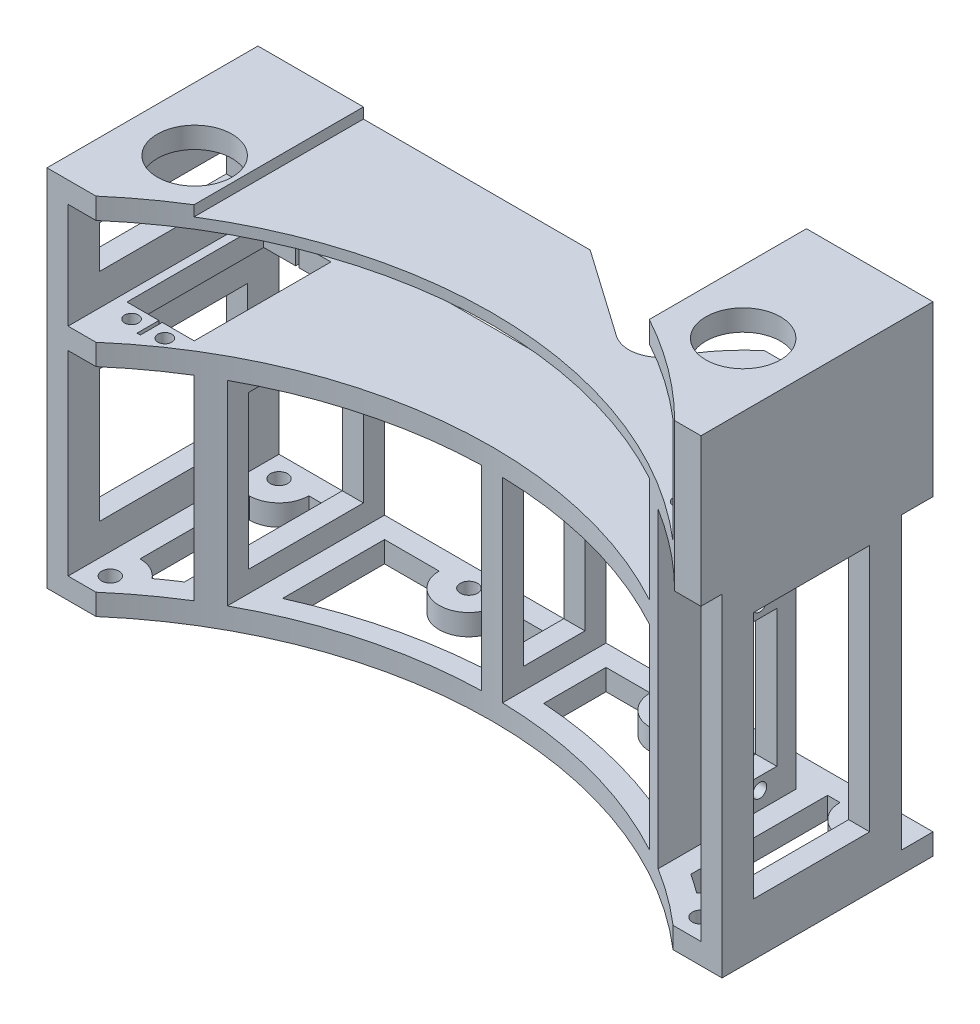
SolidWorks part; units mm, degrees
ref_plane "Front Plane" through (0, 0, 0) normal (0, 0, 1) x (1, 0, 0)
ref_plane "Top Plane" through (0, 0, 0) normal (0, 1, 0) x (1, 0, 0)
ref_plane "Right Plane" through (0, 0, 0) normal (1, 0, 0) x (0, 0, -1)
sketch "Sketch1" plane through (0, 0, 0) normal (0, 0, 1) x (1, 0, 0)
  line L0 (-101.6, 106.425) -> (101.6, 106.425)
  line L1 (-101.6, 0) -> (101.6, 0)
  line L2 (-101.6, 0) -> (-101.6, 106.425)
  line L4 (101.6, 0) -> (101.6, 106.425)
  point P5 (0, 0)
  dimension "D1" = 203.2
  dimension "D2" = 106.425
extrude "Boss-Extrude1" add sketch "Sketch1" along normal mid plane 63.5 contours L1 L4 L0 L2 | L0 region at (0, 53.2125, 0)
sketch "Sketch4" plane through (0, 0, -31.75) normal (0, 0, -1) x (-1, 0, 0)
  line L0 (-101.6, 0) -> (-101.6, 106.425) construction
  line L1 (101.6, 0) -> (101.6, 106.425) construction
  line L2 (-95.25, 103.25) -> (95.25, 103.25)
  line L3 (-95.25, 103.25) -> (-95.25, 71.5)
  line L4 (-95.25, 71.5) -> (95.25, 71.5)
  line L5 (95.25, 103.25) -> (95.25, 71.5)
  line L11 (-95.25, 65.15) -> (95.25, 65.15)
  line L12 (-95.25, 65.15) -> (-95.25, 6.35)
  line L13 (-95.25, 6.35) -> (95.25, 6.35)
  line L14 (95.25, 65.15) -> (95.25, 6.35)
  line L15 (101.6, 0) -> (-101.6, 0) construction
  dimension "D4" = 6.35
  dimension "D1" = 6.35
  dimension "D2" = 71.5
  dimension "D3" = 6.35
  dimension "D5" = 6.35
  dimension "D6" = 31.75
extrude "Cut-Extrude2" cut sketch "Sketch4" against normal through all
sketch "Sketch8" plane through (0, 0, 0) normal (0, 0, 1) x (1, 0, 0)
  line L0 (-95.25, 65.15) -> (95.25, 65.15) construction
  line L1 (-69.85, 65.15) -> (-63.5, 65.15)
  line L2 (-69.85, 65.15) -> (-69.85, 6.35)
  line L3 (-69.85, 6.35) -> (-63.5, 6.35)
  line L4 (-63.5, 65.15) -> (-63.5, 6.35)
  line L5 (95.25, 6.35) -> (-95.25, 6.35) construction
  line L6 (-95.25, 103.25) -> (95.25, 103.25) construction
  line L7 (63.5, 103.25) -> (69.85, 103.25)
  line L8 (63.5, 103.25) -> (63.5, 6.35)
  line L9 (63.5, 6.35) -> (69.85, 6.35)
  line L10 (69.85, 103.25) -> (69.85, 6.35)
  line L11 (95.25, 65.15) -> (95.25, 6.35) construction
  line L12 (-95.25, 6.35) -> (-95.25, 65.15) construction
  line L13 (-101.6, 0) -> (101.6, 0) construction
  line L14 (-3.175, 65.15) -> (3.175, 65.15)
  line L15 (-3.175, 65.15) -> (-3.175, 6.35)
  line L16 (-3.175, 6.35) -> (3.175, 6.35)
  line L17 (3.175, 65.15) -> (3.175, 6.35)
  point P24 (0, 0)
  point P25 (0, 6.35)
  dimension "D1" = 6.35
  dimension "D2" = 6.35
  dimension "D3" = 25.4
  dimension "D4" = 25.4
  dimension "D5" = 6.35
extrude "Boss-Extrude2" add sketch "Sketch8" along normal up to surface (31.75 mm away) from surface up to face at (0, 87.375, 31.75) starting at face at (0, 87.375, -31.75)
sketch "Sketch15" plane through (0, 103.25, 0) normal (0, -1, 0) x (1, 0, 0)
  line L4 (69.85, 31.75) -> (69.85, -31.75)
  line L5 (69.85, -31.75) -> (95.25, -31.75)
  line L6 (95.25, -31.75) -> (95.25, 31.75)
  line L7 (95.25, 31.75) -> (69.85, 31.75)
  line L8 (69.85, 31.75) -> (69.85, -31.75)
  line L9 (69.85, -31.75) -> (95.25, -31.75)
  line L10 (95.25, -31.75) -> (95.25, 31.75)
  line L11 (95.25, 31.75) -> (69.85, 31.75)
  dimension "D1" = 0
extrude "Boss-Extrude4" add sketch "Sketch15" along normal blind 3.175
sketch "Sketch2" plane through (0, 71.5, 0) normal (0, 1, 0) x (1, 0, 0)
  line L0 (-92.677, 24.55) -> (-72.423, -16.604) construction
  line L29 (-92.677, 24.55) -> (-83.05, 24.55)
  line L30 (-92.677, 24.55) -> (-92.677, -16.604)
  line L31 (-92.677, -16.604) -> (-83.05, -16.604)
  line L34 (-72.423, 24.55) -> (-72.423, -16.604)
  line L58 (69.85, 31.75) -> (69.85, -31.75)
  line L59 (69.85, -31.75) -> (95.25, -31.75)
  line L60 (95.25, -31.75) -> (95.25, 31.75)
  line L61 (95.25, 31.75) -> (69.85, 31.75)
  line L62 (69.85, 31.75) -> (69.85, -31.75)
  line L63 (69.85, -31.75) -> (95.25, -31.75)
  line L64 (95.25, -31.75) -> (95.25, 31.75)
  line L65 (95.25, 31.75) -> (69.85, 31.75)
  line L78 (-72.423, 24.55) -> (-92.677, -16.604) construction
  line L79 (-87.55, 28.273) -> (-77.55, -20.327) construction
  line L80 (-87.55, -20.327) -> (-77.55, 28.273) construction
  line L81 (-82.05, -16.604) -> (-72.423, -16.604)
  line L82 (-82.05, -16.604) -> (-82.05, -23.208)
  line L83 (-82.05, -23.208) -> (-83.05, -23.208)
  line L84 (-83.05, -16.604) -> (-83.05, -23.208)
  line L85 (-82.55, 3.973) -> (-13.3966, 3.973) construction
  line L86 (-82.05, 31.154) -> (-83.05, 31.154)
  line L87 (-82.05, 24.55) -> (-82.05, 31.154)
  line L88 (-83.05, 24.55) -> (-83.05, 31.154)
  line L89 (-82.05, 24.55) -> (-72.423, 24.55)
  line L90 (-101.6, -31.75) -> (101.6, -31.75) construction
  line L91 (-101.6, -31.75) -> (-101.6, 31.75) construction
  circle A12 centre (-87.55, -20.327) radius 2.1
  circle A13 centre (-77.55, -20.327) radius 2.1
  circle A14 centre (-87.55, 28.273) radius 2.1
  circle A15 centre (-77.55, 28.273) radius 2.1
  point P8 (-82.55, -23.208)
  point P17 (-82.55, 3.973)
  point P18 (-82.55, 3.973)
  point P27 (-82.55, -6.35)
  dimension "D3" = 48.6
  dimension "D4" = 4.2
  dimension "D2" = 10
  dimension "D5" = 41.154
  dimension "D6" = 20.254
  dimension "D7" = 1
  dimension "D8" = 6.604
  dimension "D9" = 30.9
  dimension "D10" = 25.4
  dimension "D11" = 0
  dimension "D12" = 19.05
extrude "Cut-Extrude3" cut sketch "Sketch2" against normal up to next
sketch "Sketch9" plane through (0, 106.425, 0) normal (0, 1, 0) x (1, 0, 0)
  line L0 (72.423, 24.55) -> (92.677, -16.604) construction
  line L1 (72.423, 24.55) -> (82.05, 24.55)
  line L2 (72.423, 24.55) -> (72.423, -16.604)
  line L3 (72.423, -16.604) -> (82.05, -16.604)
  line L4 (92.677, 24.55) -> (92.677, -16.604)
  line L5 (92.677, 24.55) -> (72.423, -16.604) construction
  line L6 (77.55, 28.273) -> (87.55, -20.327) construction
  line L7 (77.55, -20.327) -> (87.55, 28.273) construction
  line L8 (83.05, -16.604) -> (92.677, -16.604)
  line L9 (83.05, -16.604) -> (83.05, -23.208)
  line L10 (83.05, -23.208) -> (82.05, -23.208)
  line L11 (82.05, -16.604) -> (82.05, -23.208)
  line L12 (82.55, 3.973) -> (164.4034, 3.973) construction
  line L13 (83.05, 31.154) -> (82.05, 31.154)
  line L14 (83.05, 24.55) -> (83.05, 31.154)
  line L15 (82.05, 24.55) -> (82.05, 31.154)
  line L16 (83.05, 24.55) -> (92.677, 24.55)
  line L17 (101.6, -31.75) -> (101.6, 31.75) construction
  line L19 (-101.6, -31.75) -> (101.6, -31.75) construction
  circle A0 centre (77.55, -20.327) radius 2.1
  circle A1 centre (87.55, -20.327) radius 2.1
  circle A2 centre (77.55, 28.273) radius 2.1
  circle A3 centre (87.55, 28.273) radius 2.1
  point P8 (82.55, -23.208)
  point P17 (82.55, 3.973)
  point P18 (82.55, 3.973)
  point P27 (82.55, -6.35)
  dimension "D3" = 4.2
  dimension "D1" = 10
  dimension "D2" = 48.6
  dimension "D4" = 41.154
  dimension "D5" = 20.254
  dimension "D6" = 1
  dimension "D7" = 6.604
  dimension "D8" = 30.9
  dimension "D9" = 19.05
  dimension "D10" = 25.4
extrude "Cut-Extrude4" cut sketch "Sketch9" against normal up to next
sketch "Sketch12" plane through (0, 0, 0) normal (0, 1, 0) x (1, 0, 0)
  line L0 (-63.5, -31.75) -> (-63.5, 31.75) construction
  line L1 (-69.85, -31.75) -> (-95.25, -31.75) construction
  line L2 (-95.25, -31.75) -> (-95.25, 31.75) construction
  line L3 (-101.6, 31.75) -> (101.6, 31.75) construction
  circle A0 centre (-88.9, 25.4) radius 2.6
  circle A1 centre (-88.9, -25.4) radius 2.6
  circle A2 centre (-31.75, 25.4) radius 2.6
  dimension "D1" = 5.2
  dimension "D2" = 6.35
  dimension "D3" = 6.35
  dimension "D4" = 6.35
  dimension "D5" = 31.75
extrude "Cut-Extrude7" cut sketch "Sketch12" along normal up to surface (6.35 mm away) and the other way through all up to face at (-33.3375, 6.35, 0)
mirror "Mirror1" about plane through (0, 0, 0) normal (1, 0, 0) of "Cut-Extrude7"
sketch "Sketch16" plane through (0, 106.425, 0) normal (0, 1, 0) x (1, 0, 0)
  line L2 (-69.85, 31.75) -> (-101.6, 31.75)
  line L3 (-101.6, 31.75) -> (-101.6, -31.75)
  line L12 (-101.6, -31.75) -> (-69.85, -31.75)
  line L13 (-69.85, 31.75) -> (-69.85, -31.75)
  dimension "D1" = 31.75
extrude "Boss-Extrude5" add sketch "Sketch16" along normal blind 3.175
sketch "Sketch17" plane through (0, 109.6, 0) normal (0, 1, 0) x (1, 0, 0)
  line L0 (-101.6, -31.75) -> (-69.85, -31.75) construction
  line L1 (-101.6, 31.75) -> (-101.6, -31.75) construction
  circle A0 centre (-82.55, -6.35) radius 11.2395
  dimension "D3" = 22.479
  dimension "D1" = 25.4
  dimension "D2" = 19.05
extrude "Cut-Extrude8" cut sketch "Sketch17" against normal up to next
sketch "Sketch18" plane through (0, 106.425, 0) normal (0, 1, 0) x (1, 0, 0)
  line L5 (101.6, -31.75) -> (101.6, 31.75) construction
  line L6 (-69.85, -31.75) -> (101.6, -31.75) construction
  line L14 (101.6, -31.75) -> (101.6, 31.75)
  line L15 (101.6, 31.75) -> (95.25, 31.75)
  line L16 (95.25, -31.75) -> (95.25, 31.75)
  line L22 (95.25, -31.75) -> (82.55, -31.75)
  line L23 (101.6, -31.75) -> (101.6, -38.1)
  line L24 (101.6, -38.1) -> (82.55, -38.1)
  line L25 (82.55, -31.75) -> (82.55, -38.1)
  dimension "D4" = 6.35
  dimension "D5" = 19.05
extrude "Boss-Extrude6" add sketch "Sketch18" along normal blind 38.1 from surface starting at face at (87.55, 100.075, 18.227)
sketch "Sketch20" plane through (0, 138.175, 0) normal (0, 1, 0) x (1, 0, 0)
  line L1 (63.5, 31.75) -> (101.6, 31.75)
  line L2 (63.5, 31.75) -> (63.5, -38.1)
  line L3 (63.5, -38.1) -> (101.6, -38.1)
  line L4 (101.6, 31.75) -> (101.6, -38.1)
  line L6 (-69.85, -31.75) -> (82.55, -31.75) construction
  circle A0 centre (82.55, -6.35) radius 11.2395
  dimension "D2" = 19.05
  dimension "D1" = 22.479
  dimension "D4" = 38.1
  dimension "D3" = 25.4
extrude "Boss-Extrude7" add sketch "Sketch20" along normal blind 6.35
sketch "Sketch10" plane through (0, 106.425, 0) normal (0, 1, 0) x (1, 0, 0)
  circle A3 centre (0, -132.08) radius 131.1117 construction
  circle A4 centre (0, -132.08) radius 131.1117 construction
  circle A5 centre (0, -132.08) radius 132.6992
  dimension "D1" = 1.5875
extrude "Cut-Extrude5" cut sketch "Sketch10" against normal through all both and the other way through all
sketch "Sketch21" plane through (0, 106.425, 0) normal (0, 1, 0) x (1, 0, 0)
  line L5 (34.6759, 6.35) -> (-1.5991, 31.75)
  line L6 (-69.85, 31.75) -> (95.25, 31.75) construction
  line L7 (-1.5991, 31.75) -> (50.9018, 31.75)
  arc A1 (34.6759, 6.35) -> (50.9018, 31.75) centre (82.55, -6.35) cw
  dimension "D2" = 49.53
  dimension "D1" = 35
  dimension "D3" = 25.4
extrude "Cut-Extrude10" cut sketch "Sketch21" against normal up to surface (3.175 mm away) up to face at (-82.55, 103.25, 17.5895)
sketch "Sketch32" plane through (0, 6.35, 0) normal (0, 1, 0) x (1, 0, 0)
  line L8 (76.2, 25.4) -> (76.2, -15.769)
  line L9 (88.9, -25.1619) -> (88.9, 25.4)
  line L10 (88.9, 25.4) -> (76.2, 25.4)
  line L11 (76.2, 25.4) -> (76.2, -15.769)
  line L12 (88.9, -16.45) -> (88.9, 16.45)
  line L13 (79.95, 25.4) -> (76.2, 25.4)
  line L32 (-57.15, 25.4) -> (-57.15, -5.3182)
  line L33 (-9.525, 6.6426) -> (-9.525, 25.4)
  line L40 (-76.2, -15.769) -> (-76.2, 25.4)
  line L41 (-76.2, 25.4) -> (-88.9, 25.4)
  line L42 (-88.9, 25.4) -> (-88.9, -25.1619)
  line L43 (-76.2, -15.769) -> (-76.2, 25.4)
  line L44 (-76.2, 25.4) -> (-79.95, 25.4)
  line L45 (-88.9, 16.45) -> (-88.9, -16.45)
  line L48 (-9.525, 25.4) -> (-57.15, 25.4)
  line L49 (-57.15, 25.4) -> (-57.15, -5.3182)
  line L50 (-9.525, 6.6426) -> (-9.525, 25.4)
  line L67 (-9.525, 25.4) -> (-22.8, 25.4)
  line L68 (-40.7, 25.4) -> (-57.15, 25.4)
  line L69 (22.8, 25.4) -> (9.525, 25.4)
  line L71 (9.525, 25.4) -> (9.525, 6.6426)
  line L72 (57.15, -5.3181) -> (57.15, 25.4)
  line L73 (57.15, 25.4) -> (9.525, 25.4)
  line L74 (9.525, 25.4) -> (9.525, 6.6426)
  line L75 (57.15, -5.3181) -> (57.15, 25.4)
  line L76 (57.15, 25.4) -> (40.7, 25.4)
  circle A2 centre (88.9, 25.4) radius 8.95
  arc A3 (79.95, 25.4) -> (88.9, 16.45) centre (88.9, 25.4) ccw
  arc A8 (88.9, -25.1619) -> (76.2, -15.769) centre (0, -132.08) ccw
  circle A9 centre (88.9, -25.4) radius 8.95
  arc A10 (88.9, -16.45) -> (81.9575, -19.7516) centre (88.9, -25.4) ccw
  arc A11 (81.9575, -19.7516) -> (76.2, -15.769) centre (0, -132.08) ccw
  circle A13 centre (-31.75, 25.4) radius 8.95
  arc A22 (-76.2, -15.769) -> (-88.9, -25.1619) centre (0, -132.08) ccw
  arc A23 (-76.2, -15.769) -> (-81.9575, -19.7516) centre (0, -132.08) ccw
  arc A26 (-40.7, 25.4) -> (-22.8, 25.4) centre (-31.75, 25.4) ccw
  circle A27 centre (-88.9, 25.4) radius 8.95
  arc A28 (-88.9, 16.45) -> (-79.95, 25.4) centre (-88.9, 25.4) ccw
  circle A30 centre (-88.9, -25.4) radius 8.95
  arc A31 (-81.9575, -19.7516) -> (-88.9, -16.45) centre (-88.9, -25.4) ccw
  circle A33 centre (31.75, 25.4) radius 8.95
  arc A35 (22.8, 25.4) -> (40.7, 25.4) centre (31.75, 25.4) ccw
  arc A38 (-9.525, 6.6426) -> (-57.15, -5.3182) centre (0, -132.08) ccw
  arc A39 (-9.525, 6.6426) -> (-57.15, -5.3182) centre (0, -132.08) ccw
  arc A42 (57.15, -5.3181) -> (9.525, 6.6426) centre (0, -132.08) ccw
  arc A43 (57.15, -5.3181) -> (9.525, 6.6426) centre (0, -132.08) ccw
  dimension "D1" = 6.35
  dimension "D2" = 6.35
  dimension "D3" = 6.35
  dimension "D4" = 6.35
  dimension "D5" = 6.35
  dimension "D6" = 6.35
  dimension "D7" = 6.35
  dimension "D8" = 6.35
  dimension "D9" = 6.35
  dimension "D10" = 6.35
extrude "Cut-Extrude19" cut sketch "Sketch32" against normal up to next
sketch "Sketch23" plane through (0, 0, -31.75) normal (0, 0, -1) x (-1, 0, 0)
  line L1 (-101.6, 6.35) -> (-57.15, 6.35)
  line L2 (-101.6, 6.35) -> (-101.6, 93.725)
  line L3 (-101.6, 93.725) -> (-57.15, 93.725)
  line L4 (-57.15, 6.35) -> (-57.15, 93.725)
  line L7 (-63.5, 71.5) -> (95.25, 71.5) construction
  line L9 (-63.5, 65.15) -> (-63.5, 6.35) construction
  line L10 (-101.6, 0) -> (-101.6, 144.525) construction
  line L11 (-63.5, 6.35) -> (-3.175, 6.35) construction
  dimension "D1" = 6.35
  dimension "D2" = 22.225
extrude "Cut-Extrude11" cut sketch "Sketch23" against normal blind 9.525
sketch "Sketch24" plane through (63.5, 0, 0) normal (-1, 0, 0) x (0, 0, 1)
  line L0 (-16.477, 56.354) -> (3.777, 15.2) construction
  line L1 (-16.477, 56.354) -> (-6.85, 56.354)
  line L2 (-16.477, 56.354) -> (-16.477, 15.2)
  line L3 (-16.477, 15.2) -> (-6.85, 15.2)
  line L4 (3.777, 56.354) -> (3.777, 15.2)
  line L5 (3.777, 56.354) -> (-16.477, 15.2) construction
  line L6 (-11.35, 60.077) -> (-1.35, 11.477) construction
  line L7 (-11.35, 11.477) -> (-1.35, 60.077) construction
  line L8 (-5.85, 15.2) -> (3.777, 15.2)
  line L9 (-5.85, 15.2) -> (-5.85, 8.596)
  line L10 (-5.85, 8.596) -> (-6.85, 8.596)
  line L11 (-6.85, 15.2) -> (-6.85, 8.596)
  line L12 (-6.35, 35.777) -> (65.4757, 35.777) construction
  line L13 (-5.85, 62.958) -> (-6.85, 62.958)
  line L14 (-5.85, 56.354) -> (-5.85, 62.958)
  line L15 (-6.85, 56.354) -> (-6.85, 62.958)
  line L16 (-5.85, 56.354) -> (3.777, 56.354)
  line L17 (-22.225, 65.15) -> (-22.225, 6.35) construction
  line L18 (15.5603, 65.15) -> (-22.225, 65.15) construction
  circle A0 centre (-11.35, 11.477) radius 2.1
  circle A1 centre (-1.35, 11.477) radius 2.1
  circle A2 centre (-11.35, 60.077) radius 2.1
  circle A3 centre (-1.35, 60.077) radius 2.1
  point P8 (-6.35, 8.596)
  point P17 (-6.35, 35.777)
  point P18 (-6.35, 35.777)
  point P27 (-6.35, 46.1)
  dimension "D3" = 4.2
  dimension "D1" = 10
  dimension "D2" = 48.6
  dimension "D4" = 41.154
  dimension "D5" = 20.254
  dimension "D6" = 1
  dimension "D7" = 6.604
  dimension "D8" = 30.9
  dimension "D9" = 15.875
  dimension "D10" = 19.05
extrude "Cut-Extrude12" cut sketch "Sketch24" against normal up to next
sketch "Sketch26" plane through (95.25, 0, 0) normal (-1, 0, 0) x (0, 0, 1)
  line L12 (-12.7, 90.55) -> (-12.7, 15.875)
  line L13 (-12.7, 15.875) -> (22.225, 15.875)
  line L14 (22.225, 15.875) -> (22.225, 90.55)
  line L15 (22.225, 90.55) -> (-12.7, 90.55)
  line L16 (-12.7, 90.55) -> (-12.7, 15.875)
  line L17 (-12.7, 15.875) -> (22.225, 15.875)
  line L18 (22.225, 15.875) -> (22.225, 90.55)
  line L19 (22.225, 90.55) -> (-12.7, 90.55)
  dimension "D1" = 9.525
extrude "Cut-Extrude13" cut sketch "Sketch26" against normal up to next
sketch "Sketch27" plane through (63.5, 0, 0) normal (-1, 0, 0) x (0, 0, 1)
  line L12 (-15.875, 96.9) -> (-15.875, 77.85)
  line L13 (-15.875, 77.85) -> (9.2103, 77.85)
  line L14 (9.2103, 77.85) -> (9.2103, 96.9)
  line L15 (9.2103, 96.9) -> (-15.875, 96.9)
  line L16 (-15.875, 96.9) -> (-15.875, 77.85)
  line L17 (-15.875, 77.85) -> (9.2103, 77.85)
  line L18 (9.2103, 77.85) -> (9.2103, 96.9)
  line L19 (9.2103, 96.9) -> (-15.875, 96.9)
  dimension "D1" = 6.35
extrude "Cut-Extrude14" cut sketch "Sketch27" against normal up to next
sketch "Sketch28" plane through (3.175, 0, 0) normal (1, 0, 0) x (0, 0, -1)
  line L8 (25.4, 58.8) -> (6.9312, 58.8)
  line L9 (6.9312, 58.8) -> (6.9312, 12.7)
  line L10 (6.9312, 12.7) -> (25.4, 12.7)
  line L11 (25.4, 12.7) -> (25.4, 58.8)
  line L12 (25.4, 58.8) -> (6.9312, 58.8)
  line L13 (6.9312, 58.8) -> (6.9312, 12.7)
  line L14 (6.9312, 12.7) -> (25.4, 12.7)
  line L15 (25.4, 12.7) -> (25.4, 58.8)
  dimension "D1" = 6.35
extrude "Cut-Extrude15" cut sketch "Sketch28" against normal up to next
sketch "Sketch29" plane through (-63.5, 0, 0) normal (1, 0, 0) x (0, 0, -1)
  line L8 (25.4, 58.8) -> (-9.2103, 58.8)
  line L9 (-9.2103, 58.8) -> (-9.2103, 12.7)
  line L10 (-9.2103, 12.7) -> (25.4, 12.7)
  line L11 (25.4, 12.7) -> (25.4, 58.8)
  line L12 (25.4, 58.8) -> (-9.2103, 58.8)
  line L13 (-9.2103, 58.8) -> (-9.2103, 12.7)
  line L14 (-9.2103, 12.7) -> (25.4, 12.7)
  line L15 (25.4, 12.7) -> (25.4, 58.8)
  dimension "D1" = 6.35
extrude "Cut-Extrude16" cut sketch "Sketch29" against normal up to next
sketch "Sketch30" plane through (-95.25, 0, 0) normal (1, 0, 0) x (0, 0, -1)
  line L8 (22.225, 15.875) -> (22.225, 55.625)
  line L9 (22.225, 55.625) -> (-22.225, 55.625)
  line L10 (-22.225, 55.625) -> (-22.225, 15.875)
  line L11 (-22.225, 15.875) -> (22.225, 15.875)
  line L12 (22.225, 15.875) -> (22.225, 55.625)
  line L13 (22.225, 55.625) -> (-22.225, 55.625)
  line L14 (-22.225, 55.625) -> (-22.225, 15.875)
  line L15 (-22.225, 15.875) -> (22.225, 15.875)
  dimension "D1" = 9.525
extrude "Cut-Extrude17" cut sketch "Sketch30" against normal up to next
sketch "Sketch31" plane through (-95.25, 0, 0) normal (1, 0, 0) x (0, 0, -1)
  line L4 (22.225, 81.025) -> (22.225, 93.725)
  line L6 (22.225, 81.025) -> (22.225, 93.725)
  line L9 (22.225, 93.725) -> (-22.225, 93.725)
  line L10 (-22.225, 93.725) -> (-22.225, 81.025)
  line L11 (-22.225, 81.025) -> (22.225, 81.025)
  line L13 (22.225, 93.725) -> (-22.225, 93.725)
  line L14 (-22.225, 93.725) -> (-22.225, 81.025)
  line L15 (-22.225, 81.025) -> (22.225, 81.025)
  dimension "D1" = 9.525
extrude "Cut-Extrude18" cut sketch "Sketch31" against normal up to next
fillet "Fillet1" radius 9.525 1 edges at (34.6759, 104.8375, -6.35)
equation "\"tightTol\"= 0.005in"
equation "\"normTol\"= 0.01in"
equation "\"looseTol\"= 0.02in"
equation "\"D1@Sketch12\"=5.2mm"
equation "\"D2@Sketch1\"=8mm+0.5+3.25+0.125"
equation "\"D2@Sketch4\"=8mm+0.25+2.25"
equation "\"D3@Sketch17\" = 7 / 8 + \"normTol\""
equation "\"D1@Sketch20\"=7/8+\"normTol\""
